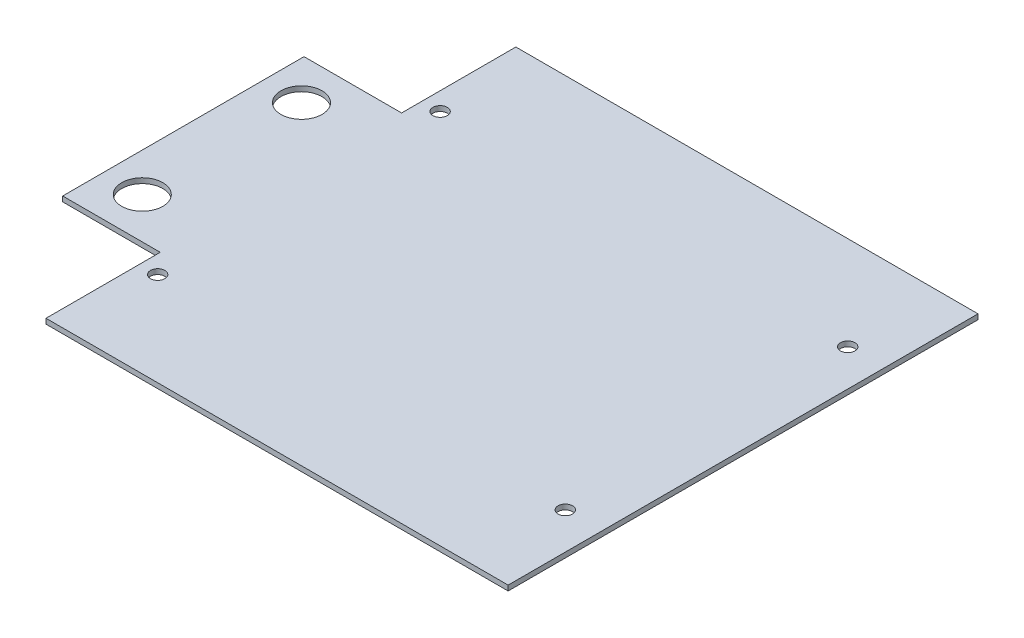
SolidWorks part; units mm, degrees
ref_plane "Front Plane" through (0, 0, 0) normal (0, 0, 1) x (1, 0, 0)
ref_plane "Top Plane" through (0, 0, 0) normal (0, 1, 0) x (1, 0, 0)
ref_plane "Right Plane" through (0, 0, 0) normal (1, 0, 0) x (0, 0, -1)
sketch "Sketch1" plane through (0, 0, 0) normal (0, 1, 0) x (1, 0, 0)
  line L1 (-90, 91.5) -> (90, 91.5)
  line L3 (-90, -91.5) -> (90, -91.5)
  line L4 (90, 91.5) -> (90, -91.5)
  line L5 (0, -91.5) -> (0, 91.5) construction
  line L6 (-90, 0) -> (90, 0) construction
  line L7 (-83, -55.0037) -> (75.76, -55.0037) construction
  line L8 (75.76, -55.0037) -> (75.76, 55.0037) construction
  line L9 (75.76, 55.0037) -> (-83, 55.0037) construction
  line L10 (-83, 55.0037) -> (-83, -55.0037) construction
  line L11 (-90, 91.5) -> (-90, 47)
  line L12 (-90, 47) -> (-128, 47)
  line L13 (-128, 47) -> (-128, -47)
  line L14 (-128, -47) -> (-90, -47)
  line L15 (-90, -47) -> (-90, -91.5)
  line L16 (-113, 31) -> (-113, -31) construction
  circle A0 centre (-83, 55.0037) radius 2.8
  circle A1 centre (-83, -55.0037) radius 2.8
  circle A2 centre (75.76, -55.0037) radius 2.8
  circle A3 centre (75.76, 55.0037) radius 2.8
  circle A4 centre (-113, 31) radius 8
  circle A6 centre (-113, -31) radius 8
  arc A7 (-83, 52.2097) -> (-83, 57.7977) centre (-83, 55.0037) ccw construction
  arc A8 (-83, 52.2097) -> (-83, 57.7977) centre (-83, 55.0037) ccw construction
  arc A9 (72.9629, -55.0037) -> (75.7569, -57.7977) centre (75.7569, -55.0037) ccw construction
  arc A10 (72.9629, 55.0037) -> (75.7569, 52.2097) centre (75.7569, 55.0037) ccw construction
  arc A11 (72.9629, -55.0037) -> (75.7569, -57.7977) centre (75.7569, -55.0037) ccw construction
  arc A12 (72.9629, 55.0037) -> (75.7569, 52.2097) centre (75.7569, 55.0037) ccw construction
  point P0 (0, 0)
  point P12 (-113, 0)
  point P16 (75.76, 0)
  point P22 (0, 0)
  point P23 (108.1609, 91.5)
  point P24 (-93.8413, 54.3287)
  point P25 (63.7991, 55)
  point P26 (63.9636, -55)
  point P27 (-93.8413, 54.3287)
  point P37 (-106.1694, -47)
  point P38 (-118.6647, 23.5442)
  point P40 (-122.5, 30.8107)
  dimension "D1" = 158.76
  dimension "D5" = 5.6
  dimension "D9" = 16
  dimension "D11" = 15
  dimension "D2" = 183
  dimension "D3" = 110.0074
  dimension "D4" = 38
  dimension "D6" = 94
  dimension "D7" = 180
  dimension "D8" = 7
  dimension "D10" = 62
base flange "Base-Flange1" sketch "Sketch1" thickness 2 reverse thickness direction no parameters "D1"=2
sketch "Bend-Lines1" [suppressed] plane through (0, 0, 0) normal (0, 1, 0) x (1, 0, 0)
sketch "Bounding-Box1" [suppressed] plane through (0, 0, 0) normal (0, 1, 0) x (1, 0, 0)
sheet metal parameters "Sheet-Metal1" thickness 2 parameters "D1"=2
flat pattern "Flat-Pattern1" [suppressed]
sketch "Bend-Lines2" plane through (0, 0, 0) normal (0, 1, 0) x (1, 0, 0)
sketch3d "Bounding-Box2" [suppressed]
  line L0 (90, -91.5, 0) -> (-128, -91.5, 0) construction
  line L1 (90, 91.5, 0) -> (-128, 91.5, 0) construction
  line L2 (90, -91.5, 0) -> (90, 91.5, 0) construction
  line L3 (-128, -91.5, 0) -> (-128, 91.5, 0) construction
